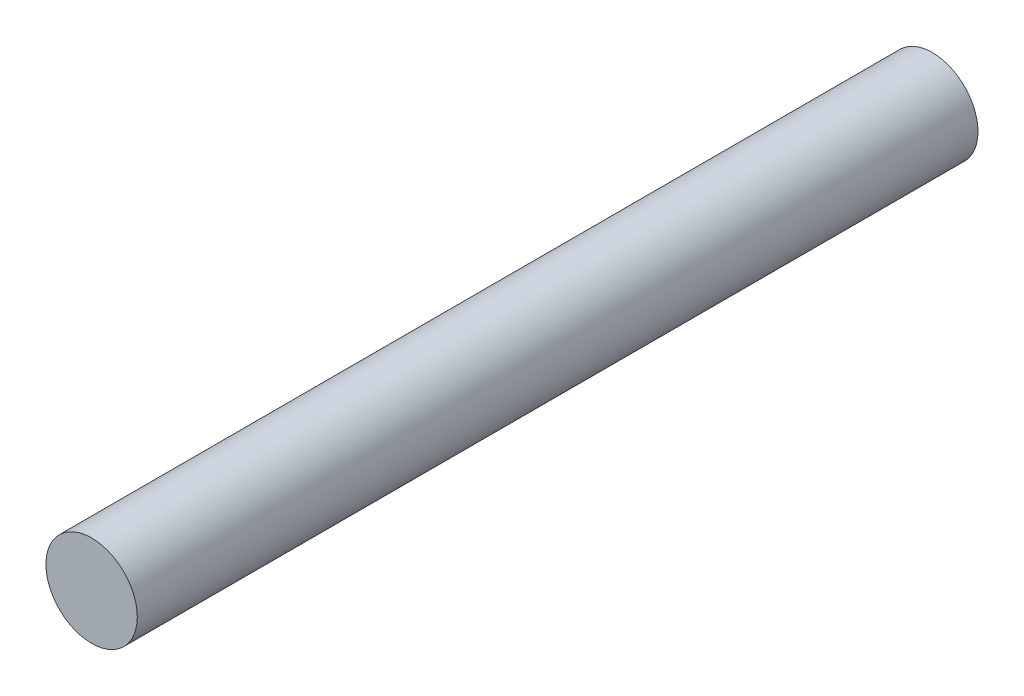
SolidWorks part; units mm, degrees
ref_plane "xy_plane" through (0, 0, 0) normal (0, 0, 1) x (1, 0, 0)
ref_plane "zx_plane" through (0, 0, 0) normal (0, 1, 0) x (1, 0, 0)
ref_plane "yz_plane" through (0, 0, 0) normal (1, 0, 0) x (0, 0, -1)
ref_axis "x_axis" through (-80.9, 0, 0) along (1, 0, 0)
ref_axis "y_axis" through (0, -50, 0) along (0, 1, 0)
ref_axis "z_axis" through (0, 0, -80.9) along (0, 0, 1)
sketch "pivotShaft_sketch" plane through (0, 0, 0) normal (0, 0, 1) x (1, 0, 0)
  circle A0 centre (0, 0) radius 2.5
  point P2 (0, 0)
extrude "pivotShaft_extrude" add sketch "pivotShaft_sketch" along normal mid plane 46
equation "\"D1@pivotShaft_sketch\"=\"externalParameters.this.diameter\""
equation "\"D1@pivotShaft_extrude\"=\"externalParameters.this.length\""
